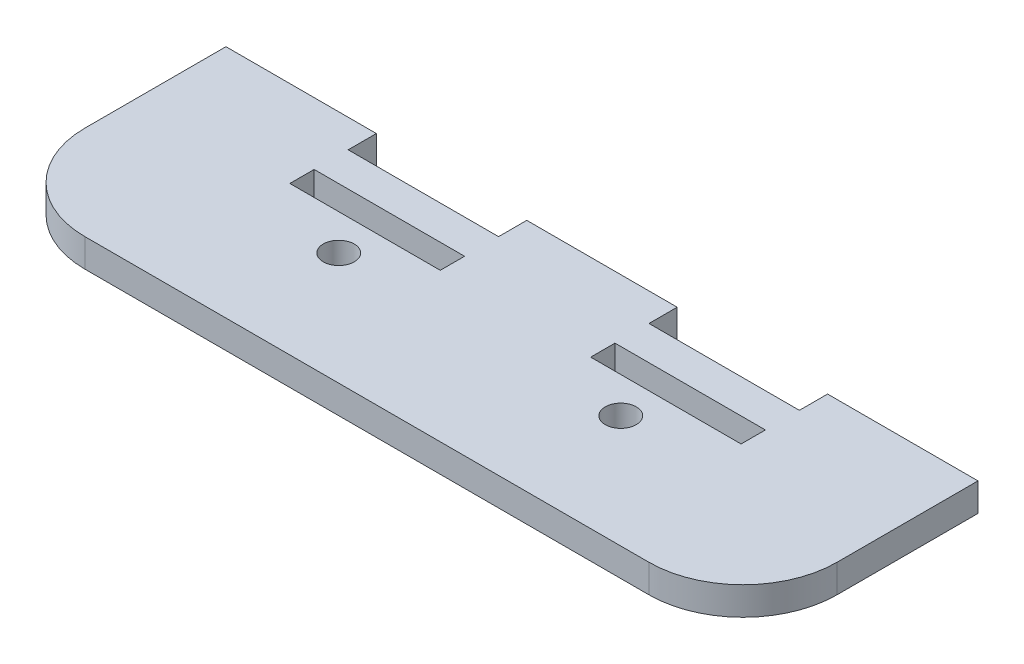
SolidWorks part; units mm, degrees
ref_plane "Ön Düzlem" through (0, 0, 0) normal (0, 0, 1) x (1, 0, 0)
ref_plane "Üst Düzlem" through (0, 0, 0) normal (0, 1, 0) x (1, 0, 0)
ref_plane "Sağ Düzlem" through (0, 0, 0) normal (1, 0, 0) x (0, 0, -1)
sketch "Sketch1" plane through (0, 0, 0) normal (0, 1, 0) x (1, 0, 0)
  line L0 (-40, 12.5) -> (-40, 9.5) construction
  line L1 (30, -12.5) -> (-30, -12.5)
  line L2 (40, -2.5) -> (40, 12.5)
  line L3 (40, 12.5) -> (24, 12.5)
  line L4 (-40, -2.5) -> (-40, 12.5)
  line L5 (40, -12.5) -> (-40, 12.5) construction
  line L6 (40, 12.5) -> (-40, -12.5) construction
  line L7 (-40, 9.5) -> (-40, 5.8835) construction
  line L8 (-40, 5.8835) -> (-40, 3.2973) construction
  line L9 (-40, 3.2973) -> (40, 3.2973) construction
  line L10 (-40, 5.8835) -> (40, 5.8835) construction
  line L11 (-40, 9.5) -> (40, 9.5) construction
  line L12 (-40, 9.5) -> (-24, 9.5) construction
  line L13 (-24, 9.5) -> (-24, 12.5)
  line L14 (-24, 9.5) -> (-8, 9.5)
  line L15 (-8, 9.5) -> (-8, 12.5)
  line L16 (40, 9.5) -> (24, 9.5) construction
  line L17 (24, 9.5) -> (24, 12.5)
  line L18 (24, 9.5) -> (8, 9.5)
  line L19 (8, 9.5) -> (8, 12.5)
  line L20 (-24, 12.5) -> (-40, 12.5)
  line L21 (8, 12.5) -> (-8, 12.5)
  line L22 (-24, 5.8835) -> (-24, 3.2973)
  line L23 (-24, 3.2973) -> (-8, 3.2973)
  line L24 (-8, 3.2973) -> (-8, 5.8835)
  line L25 (-8, 5.8835) -> (-24, 5.8835)
  line L26 (8, 5.8835) -> (8, 3.2973)
  line L27 (8, 3.2973) -> (24, 3.2973)
  line L28 (24, 3.2973) -> (24, 5.8835)
  line L29 (24, 5.8835) -> (8, 5.8835)
  circle A0 centre (-15, -0.5) radius 1.65
  circle A1 centre (15, -0.5) radius 1.65
  arc A2 (-40, -2.5) -> (-30, -12.5) centre (-30, -2.5) ccw
  arc A3 (40, -2.5) -> (30, -12.5) centre (30, -2.5) cw
  point P0 (0, 0)
  point P36 (0, 0)
  point P39 (25.277, 5.9486)
  point P40 (24, 5.8835)
  dimension "D3" = 10
  dimension "D4" = 10
  dimension "D1" = 25
  dimension "D2" = 80
extrude "Boss-Extrude1" add sketch "Sketch1" along normal blind 3
